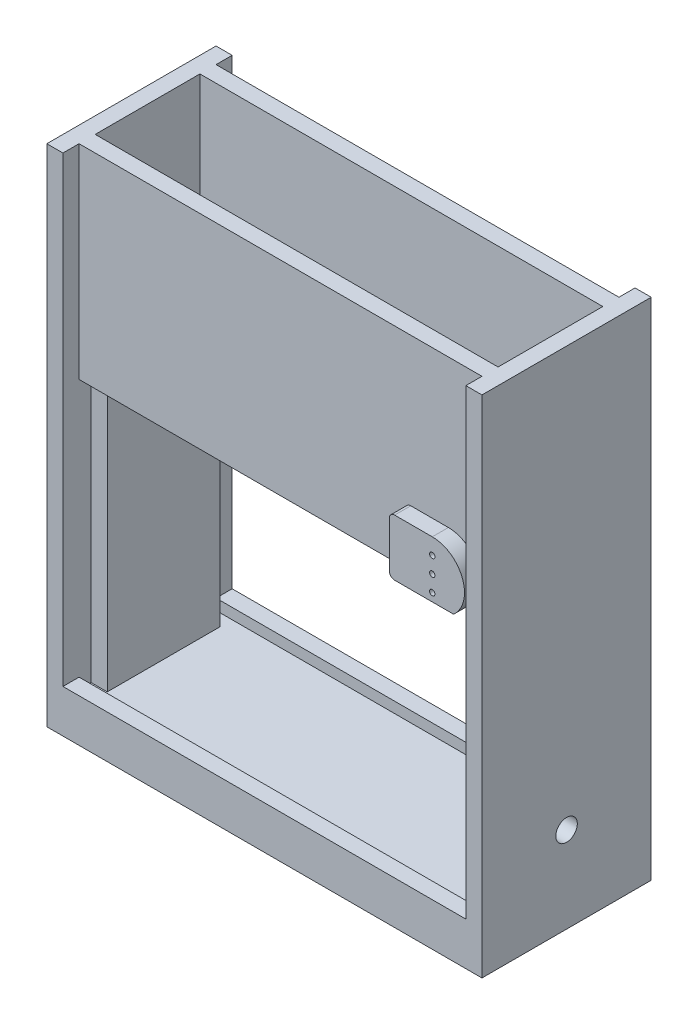
SolidWorks part; units mm, degrees
note: The reader was unsure of these and kept them because the rebuilt part matched: shared geometry of "Sketch1<2>", "Sketch7<3>", "Sketch16<2>".
ref_plane "Front Plane" through (0, 0, 0) normal (0, 0, 1) x (1, 0, 0)
ref_plane "Top Plane" through (0, 0, 0) normal (0, 1, 0) x (1, 0, 0)
ref_plane "Right Plane" through (0, 0, 0) normal (1, 0, 0) x (0, 0, -1)
sketch "Sketch1" plane through (0, 0, 0) normal (0, 1, 0) x (1, 0, 0)
  line L1 (-75, -21) -> (75, -21)
  line L2 (-75, -21) -> (-75, 21)
  line L3 (-75, 21) -> (75, 21)
  line L4 (75, -21) -> (75, 21)
  line L5 (-75, -21) -> (75, 21) construction
  line L6 (-75, 21) -> (75, -21) construction
  point P0 (0, 0)
  dimension "D1" = 42
  dimension "D2" = 150
extrude "Boss-Extrude1" add sketch "Sketch1" along normal blind 3.2
sketch "Sketch2" plane through (0, 0, 0) normal (0, -1, 0) x (1, 0, 0)
  line L0 (75, 21) -> (75, -21) construction
  line L1 (-81, 25.5) -> (81, 25.5)
  line L2 (-81, 25.5) -> (-81, -25.5)
  line L3 (-81, -25.5) -> (81, -25.5)
  line L4 (81, 25.5) -> (81, -25.5)
  line L5 (-81, 25.5) -> (81, -25.5) construction
  line L6 (-81, -25.5) -> (81, 25.5) construction
  line L7 (75, -21) -> (-75, -21) construction
  point P0 (0, 0)
  dimension "D1" = 6
  dimension "D2" = 4.5
extrude "Boss-Extrude2" add sketch "Sketch2" along normal blind 6
sketch "Sketch4" plane through (0, 0, -21) normal (0, 0, -1) x (-1, 0, 0)
  line L1 (-75, 0) -> (75, 0)
  line L2 (-75, 0) -> (-75, 100)
  line L3 (-75, 100) -> (75, 100)
  line L4 (75, 0) -> (75, 100)
  line L5 (-75, 100) -> (75, 100)
  line L6 (-75, 100) -> (-75, 106)
  line L7 (-75, 106) -> (75, 106)
  line L8 (75, 100) -> (75, 106)
  line L9 (-75, 106) -> (75, 106)
  line L10 (-75, 106) -> (-75, 176)
  line L11 (-75, 176) -> (75, 176)
  line L12 (75, 106) -> (75, 176)
  point P5 (73.6966, 106)
  dimension "D1" = 100
  dimension "D2" = 6
  dimension "D3" = 70
sketch "Sketch3" plane through (0, 0, 0) normal (0, 1, 0) x (1, 0, 0)
  line L0 (-81, 25.5) -> (81, 25.5) construction
  line L1 (81, -25.5) -> (75, -25.5)
  line L2 (81, -25.5) -> (81, 25.5)
  line L3 (81, 25.5) -> (75, 25.5)
  line L4 (75, -25.5) -> (75, 25.5)
  line L5 (75, -21) -> (75, 21) construction
  line L6 (-81, -25.5) -> (-75, -25.5)
  line L7 (-81, -25.5) -> (-81, 25.5)
  line L8 (-81, 25.5) -> (-75, 25.5)
  line L9 (-75, -25.5) -> (-75, 25.5)
  line L10 (-75, 21) -> (-75, -21) construction
extrude "Boss-Extrude3" add sketch "Sketch3" along normal up to vertex (176 mm away) up to point (75, 176, -21)
sketch "Sketch5" plane through (75, 0, 0) normal (-1, 0, 0) x (0, 0, 1)
  line L0 (-25.5, 176) -> (-25.5, 0) construction
  line L1 (-25.5, 100) -> (25.5, 100)
  line L2 (-25.5, 100) -> (-25.5, 106)
  line L3 (-25.5, 106) -> (25.5, 106)
  line L4 (25.5, 100) -> (25.5, 106)
  line L5 (25.5, 176) -> (25.5, 0) construction
extrude "Boss-Extrude4" add sketch "Sketch5" along normal up to next
extrude "Boss-Extrude5" add sketch "Sketch1<2>" against normal blind 3.2 from surface at 100 starting at face at (0, 100, 0)
sketch "Sketch1<2>" plane through (0, 0, 0) normal (0, 1, 0) x (1, 0, 0) same geometry as "Sketch1"
sketch "Sketch6" plane through (0, 106, 0) normal (0, 1, 0) x (1, 0, 0)
  line L0 (-75, -25.5) -> (-75, 25.5) construction
  line L1 (75, -25.5) -> (-75, -25.5)
  line L2 (75, -25.5) -> (75, -19.5)
  line L3 (75, -19.5) -> (-75, -19.5)
  line L4 (-75, -25.5) -> (-75, -19.5)
  line L5 (75, -25.5) -> (75, 25.5) construction
  line L6 (-75, 25.5) -> (75, 25.5)
  line L7 (-75, 25.5) -> (-75, 19.5)
  line L8 (-75, 19.5) -> (75, 19.5)
  line L9 (75, 25.5) -> (75, 19.5)
  dimension "D1" = 6
extrude "Boss-Extrude6" add sketch "Sketch6" along normal up to surface (70 mm away) up to face at (78, 176, 0)
sketch "Sketch7" plane through (0, 106, 0) normal (0, 1, 0) x (1, 0, 0)
  line L0 (75, 0) -> (-75, 0) construction
  line L1 (75, -10) -> (75, -19.5) construction
  line L2 (-75, 10) -> (75, 10) construction
  line L3 (-75, 10) -> (-75, -10) construction
  line L4 (75, 19.5) -> (-75, 19.5)
  line L5 (-75, 19.5) -> (-75, -19.5)
  line L6 (-75, -19.5) -> (75, -19.5)
  line L7 (75, -19.5) -> (75, 19.5)
  line L8 (75, 19.5) -> (-75, 19.5) construction
  line L9 (-75, 19.5) -> (-75, -19.5) construction
  line L10 (-75, -19.5) -> (75, -19.5) construction
  line L11 (75, -19.5) -> (75, 19.5) construction
  line L12 (-75, -10) -> (75, -10) construction
  line L13 (75, 10) -> (75, -10) construction
  line L14 (-75, 10) -> (75, -10) construction
  line L15 (-75, -10) -> (75, 10) construction
  line L16 (75, -19.5) -> (65.5, -19.5) construction
  line L17 (65.5, -19.5) -> (65.5, -10) construction
  line L18 (65.5, -19.5) -> (75, -10) construction
  line L19 (70.25, -17.5) -> (70.25, -19.5) construction
  line L21 (65.5, -19.5) -> (59.5, -19.5)
  line L22 (65.5, -19.5) -> (65.5, 19.5)
  line L23 (65.5, 19.5) -> (59.5, 19.5)
  line L24 (59.5, -19.5) -> (59.5, 19.5)
  line L25 (75, -19.5) -> (65.5, -19.5)
  line L26 (75, -19.5) -> (75, 19.5)
  line L27 (75, 19.5) -> (65.5, 19.5)
  line L28 (65.5, -19.5) -> (65.5, 19.5)
  circle A0 centre (70.25, -14.75) radius 2.75
  circle A1 centre (70.25, 14.75) radius 2.75
  point P6 (0, 0)
  line M16 (75, 19.5) -> (-75, 19.5)
  line M18 (-75, -19.5) -> (75, -19.5)
  line M19 (75, -19.5) -> (75, 19.5)
  dimension "D2" = 20
  dimension "D3" = 2
  dimension "D4" = 6
  dimension "D1" = 0
extrude "Cut-Extrude1" cut sketch "Sketch7" against normal up to next contours L22 A0 A1 M18 M19 M16 | A0 | A1
extrude "Boss-Extrude7" add sketch "Sketch7<3>" along normal offset from surface (54 mm away) 16 contours L24 L22 M18 M16 up to face at (0, 176, 0)
sketch "Sketch7<3>" plane through (0, 106, 0) normal (0, 1, 0) x (1, 0, 0) same geometry as "Sketch7"
sketch "Sketch8" plane through (0, 0, -25.5) normal (0, 0, -1) x (-1, 0, 0)
  line L0 (81, -6) -> (81, 176) construction
  line L1 (-81, -6) -> (81, -6)
  line L2 (-81, -6) -> (-81, 4)
  line L3 (-81, 4) -> (81, 4)
  line L4 (81, -6) -> (81, 4)
  dimension "D1" = 10
extrude "Boss-Extrude8" add sketch "Sketch8" along normal blind 6
mirror "Mirror1" about plane through (0, 0, 0) normal (0, 0, 1) of "Boss-Extrude8"
sketch "Sketch9" plane through (0, 3.2, 0) normal (0, 1, 0) x (1, 0, 0)
  line L4 (75, -21) -> (75, 21)
  line L5 (75, 21) -> (-75, 21)
  line L6 (-75, 21) -> (-75, -21)
  line L7 (-75, -21) -> (75, -21)
  line L8 (75, -21) -> (75, 21)
  line L9 (75, 21) -> (-75, 21)
  line L10 (-75, 21) -> (-75, -21)
  line L11 (-75, -21) -> (75, -21)
  dimension "D1" = 0
extrude "Cut-Extrude2" cut sketch "Sketch9" against normal up to surface (3.2 mm away) up to face at (0, 0, -23.25)
sketch "Sketch10" plane through (0, 96.8, 0) normal (0, -1, 0) x (1, 0, 0)
  line L4 (-75, -21) -> (75, -21)
  line L5 (75, -21) -> (75, -19.5)
  line L6 (75, 21) -> (-75, 21)
  line L7 (-75, 21) -> (-75, -21)
  line L8 (-75, -21) -> (75, -21)
  line L9 (75, -21) -> (75, -19.5)
  line L10 (75, 21) -> (-75, 21)
  line L11 (-75, 21) -> (-75, -21)
  line L16 (65.5, 19.5) -> (75, 19.5)
  line L17 (65.5, 19.5) -> (75, 19.5)
  line L18 (75, 19.5) -> (75, 21)
  line L19 (75, 19.5) -> (75, 21)
  line L20 (75, -19.5) -> (65.5, -19.5)
  line L21 (75, -19.5) -> (65.5, -19.5)
  line L22 (65.5, -19.5) -> (65.5, 19.5)
  line L23 (65.5, -19.5) -> (65.5, 19.5)
  dimension "D1" = 0
extrude "Cut-Extrude3" cut sketch "Sketch10" against normal up to surface (3.2 mm away) up to face at (0, 100, -23.25)
sketch "Sketch11" plane through (75, 0, 0) normal (-1, 0, 0) x (0, 0, 1)
  line L0 (-25.5, 0) -> (25.5, 0) construction
  line L1 (-21, 93.5) -> (21, 93.5)
  line L2 (-21, 93.5) -> (-21, 0)
  line L3 (-21, 0) -> (21, 0)
  line L4 (21, 93.5) -> (21, 0)
  line L6 (-25.5, 100) -> (-19.5, 100) construction
  line L7 (0, 93.5) -> (0, 100) construction
  line L8 (10, 93.5) -> (10, 100)
  line L9 (10, 100) -> (21, 100)
  line L10 (21, 100) -> (21, 93.5)
  point P5 (0, 0)
  point P13 (0, 0)
  line M8 (25.5, 100) -> (19.5, 100)
  line M11 (-25.5, 0) -> (25.5, 0)
  dimension "D1" = 42
  dimension "D2" = 6.5
  dimension "D3" = 10
extrude "Boss-Extrude9" add sketch "Sketch11" along normal blind 6 contours L4 L1 L2 M11 | L10 L8 L1 M8
mirror "Mirror2" about plane through (0, 0, 0) normal (1, 0, 0) of "Boss-Extrude9"
sketch "Sketch12" plane through (0, 100, 0) normal (0, 1, 0) x (1, 0, 0)
  line L4 (69, -10) -> (69, -19.5)
  line L5 (69, -19.5) -> (75, -19.5)
  line L6 (75, -19.5) -> (75, -10)
  line L7 (75, -10) -> (69, -10)
  line L8 (69, -10) -> (69, -19.5)
  line L9 (69, -19.5) -> (75, -19.5)
  line L10 (75, -19.5) -> (75, -10)
  line L11 (75, -10) -> (69, -10)
  dimension "D1" = 0
extrude "Boss-Extrude10" add sketch "Sketch12" along normal blind 6
sketch "Sketch13" plane through (69, 0, 0) normal (-1, 0, 0) x (0, 0, 1)
  line L0 (0, 20) -> (0, 0) construction
  line L1 (-21, 0) -> (21, 0) construction
  circle A0 centre (0, 20) radius 4
  point P2 (0, 0)
  dimension "D1" = 8
  dimension "D2" = 20
extrude "Cut-Extrude4" cut sketch "Sketch13" against normal up to next contours A0
sketch "Sketch14" plane through (0, 0, -19.5) normal (0, 0, 1) x (1, 0, 0)
  line L8 (65.5, 100) -> (59.5, 106) construction
  line L9 (59.5, 106) -> (65.5, 112) construction
  line L10 (65.5, 112) -> (59.5, 118) construction
  line L16 (65.5, 160) -> (65.5, 100)
  line L17 (65.5, 100) -> (75, 100)
  line L18 (75, 100) -> (75, 176)
  line L19 (75, 176) -> (-75, 176)
  line L20 (-75, 176) -> (-75, 106)
  line L21 (-75, 106) -> (59.5, 106)
  line L22 (59.5, 106) -> (59.5, 160)
  line L23 (59.5, 160) -> (65.5, 160)
  line L24 (65.5, 160) -> (65.5, 100) construction
  line L25 (65.5, 100) -> (75, 100) construction
  line L26 (75, 100) -> (75, 176) construction
  line L27 (75, 176) -> (-75, 176) construction
  line L28 (-75, 176) -> (-75, 106) construction
  line L29 (-75, 106) -> (59.5, 106) construction
  line L30 (59.5, 106) -> (59.5, 160) construction
  line L31 (59.5, 160) -> (65.5, 160) construction
  circle A0 centre (62.5, 103) radius 1
  circle A1 centre (62.5, 109) radius 1
  circle A2 centre (62.5, 115) radius 1
  dimension "D2" = 2
  dimension "D1" = 0
extrude "Cut-Extrude5" cut sketch "Sketch14" against normal up to next
sketch "Sketch15" plane through (0, 0, -25.5) normal (0, 0, -1) x (-1, 0, 0)
  line L0 (-70.4373, 100) -> (-54.5627, 100)
  line L1 (75, 100) -> (-75, 100) construction
  line L2 (-62.5, 97) -> (-62.5, 100) construction
  line L3 (-54.5627, 100) -> (-46.5, 100)
  line L4 (-46.5, 100) -> (-46.5, 121)
  line L5 (-46.5, 121) -> (-62.5, 121)
  line L6 (-75, 100) -> (-75, 109) construction
  line L7 (-75, 109) -> (-74.5, 109) construction
  arc A0 (-70.4373, 100) -> (-54.5627, 100) centre (-62.5, 109) cw
  arc A1 (-54.5627, 100) -> (-70.4373, 100) centre (-62.5, 109) cw construction
  circle M4 centre (-62.5, 103) radius 1
  circle M5 centre (-62.5, 109) radius 1
  circle M6 centre (-62.5, 115) radius 1
  line M13 (-75, 100) -> (75, 100)
  dimension "D1" = 0.5
  dimension "D2" = 3
  dimension "D3" = 16
sketch "Sketch16" plane through (0, 0, -25.5) normal (0, 0, -1) x (-1, 0, 0)
  line L1 (75, 4) -> (81, 4)
  line L2 (75, 4) -> (75, 176)
  line L3 (75, 176) -> (81, 176)
  line L4 (81, 4) -> (81, 176)
  line L5 (-81, 176) -> (-75, 176)
  line L6 (-81, 176) -> (-81, 4)
  line L7 (-81, 4) -> (-75, 4)
  line L8 (75, 4) -> (81, 4)
  line L9 (81, 4) -> (81, 176)
  line L10 (81, 176) -> (-81, 176)
  line L11 (-81, 176) -> (-81, 4)
  line L12 (-81, 4) -> (-75, 4)
  line L13 (-75, 4) -> (-75, 100)
  line L14 (-75, 100) -> (75, 100)
  line L15 (75, 100) -> (75, 4)
  line L16 (75, 4) -> (81, 4) construction
  line L17 (81, 4) -> (81, 176) construction
  line L18 (81, 176) -> (-81, 176) construction
  line L19 (-81, 176) -> (-81, 4) construction
  line L20 (-81, 4) -> (-75, 4) construction
  line L21 (-75, 4) -> (-75, 100) construction
  line L22 (-75, 100) -> (75, 100) construction
  line L23 (75, 100) -> (75, 4) construction
  line L24 (-75, 176) -> (-75, 4)
  dimension "D1" = 0
extrude "Boss-Extrude11" add sketch "Sketch16" along normal up to surface (6 mm away) up to face at (0, -1, -31.5)
extrude "Boss-Extrude15" add sketch "Sketch16<2>" against normal up to surface (6 mm away) from surface at -51
sketch "Sketch16<2>" plane through (0, 0, -25.5) normal (0, 0, -1) x (-1, 0, 0) same geometry as "Sketch16"
sketch "Sketch17" plane through (0, -6, 0) normal (0, -1, 0) x (1, 0, 0)
  line L0 (-81, 31.5) -> (-81, -31.5) construction
  line L1 (75, -28.3) -> (-75, -28.3)
  line L2 (75, -28.3) -> (75, 28.3)
  line L3 (75, 28.3) -> (-75, 28.3)
  line L4 (-75, -28.3) -> (-75, 28.3)
  line L5 (75, -28.3) -> (-75, 28.3) construction
  line L6 (75, 28.3) -> (-75, -28.3) construction
  line L7 (81, -31.5) -> (-81, -31.5) construction
  point P0 (0, 0)
  line M3 (81, -31.5) -> (81, 31.5)
  line M4 (81, 31.5) -> (-81, 31.5)
  line M5 (-81, 31.5) -> (-81, -31.5)
  line M6 (-81, -31.5) -> (81, -31.5)
  dimension "D1" = 6
  dimension "D2" = 3.2
extrude "Boss-Extrude12" add sketch "Sketch17" along normal blind 6 contours L1 L4 L3 L2 M6 M3 M4 M5
extrude "Boss-Extrude14" add sketch "Sketch15" along normal blind 6 contours L5 A0 L4 M13 | A0 M13 M5 M6 M4
fillet "Fillet1" radius 2 2 edges at (46.5, 100, -28.5) (46.5, 121, -28.5)
mirror "Mirror4" about plane through (0, 0, 0) normal (0, 0, 1) of "Fillet1", "Boss-Extrude14"
sketch "Sketch18" plane through (0, 176, 0) normal (0, 1, 0) x (1, 0, 0)
  line L0 (-74.5, 19) -> (-74.5, -19)
  line L1 (75, -31.5) -> (-75, -31.5)
  line L2 (75, -31.5) -> (75, 31.5)
  line L3 (75, 31.5) -> (-75, 31.5)
  line L4 (-75, -31.5) -> (-75, 31.5)
  line L5 (-75, 19.5) -> (75, 19.5) construction
  line L6 (-75, 19.5) -> (-75, -19.5) construction
  line L7 (-75, -19.5) -> (75, -19.5) construction
  line L8 (75, 19.5) -> (75, -19.5) construction
  line L9 (-74.5, -19) -> (74.5, -19)
  line L10 (74.5, 19) -> (74.5, -19)
  line L11 (-74.5, 19) -> (74.5, 19)
  point P16 (0, 0)
  point P17 (75, -31.5)
  point P19 (0, 0)
  point P20 (-75, 31.5)
  dimension "D1" = 0.5
equation "\"glass_width\" = 150"
equation "\"glass_height\"= 100"
equation "\"glass_thickness\"= 4"
equation "\"brood_space\"= 42"
equation "\"t1\"= 6"
equation "\"t2\"= 6"
equation "\"D2@Sketch2\"=0.5+ \"glass_thickness\""
equation "\"foodchamber_height\"= 70"
equation "\"D2@Sketch11\"=\"t1\"+0.5"
equation "\"D1@Boss-Extrude8\"=\"t2\""
